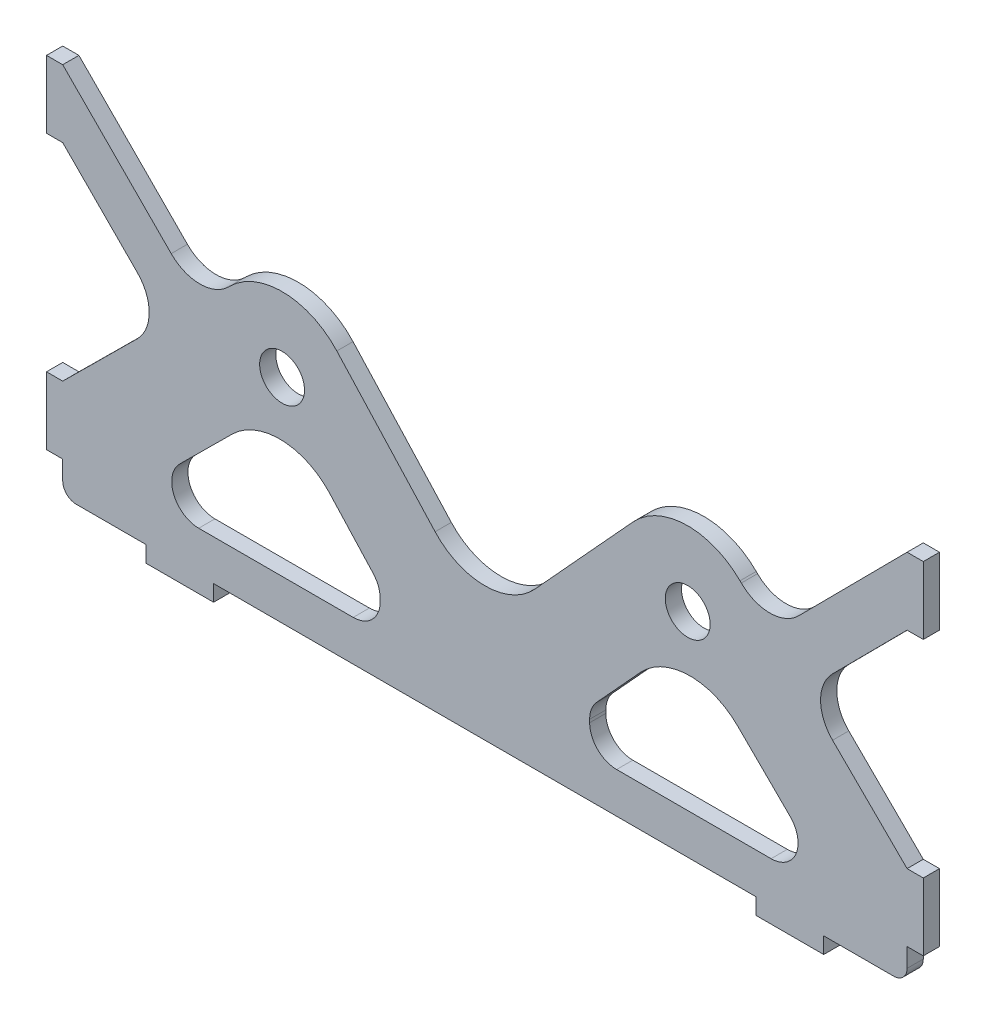
SolidWorks part; units mm, degrees
material "AISI 1020"
ref_plane "Front Plane" through (0, 0, 0) normal (0, 0, 1) x (1, 0, 0)
ref_plane "Top Plane" through (0, 0, 0) normal (0, 1, 0) x (1, 0, 0)
ref_plane "Right Plane" through (0, 0, 0) normal (1, 0, 0) x (0, 0, -1)
sketch "Sketch1" plane through (0, 0, 0) normal (0, 0, 1) x (1, 0, 0)
  line L1 (-79.4411, 19.05) -> (-79.4411, 57.404) construction
  line L5 (51.054, 0) -> (-51.054, 0)
  line L6 (-51.054, 0) -> (-51.054, -3.048)
  line L7 (-51.054, -3.048) -> (-63.754, -3.048)
  line L8 (-63.754, -3.048) -> (-63.754, 0)
  line L9 (-63.754, 0) -> (-76.9011, 0)
  line L10 (-79.4411, 2.54) -> (-79.4411, 6.096)
  line L11 (-79.4411, 6.096) -> (-82.4891, 6.096)
  line L12 (-82.4891, 6.096) -> (-82.4891, 18.796)
  line L13 (-82.4891, 18.796) -> (-79.4411, 18.796)
  line L15 (-82.4891, 19.05) -> (-82.4891, 57.404) construction
  line L16 (-64.008, -3.048) -> (-76.7741, -3.048) construction
  line L17 (-79.4411, 18.796) -> (-48.0051, 49.9833)
  line L18 (-27.8597, 49.4966) -> (0, 19.05)
  line L19 (-82.4891, 19.05) -> (-79.4411, 19.05) construction
  line L20 (-50.8, -3.048) -> (-50.8, 0) construction
  line L21 (-79.4411, 2.667) -> (-79.4411, 5.842) construction
  line L22 (0, -1000) -> (0, 49000) construction
  line L23 (27.8597, 49.4966) -> (0, 19.05)
  line L24 (79.4411, 18.796) -> (48.0051, 49.9833)
  line L25 (82.4891, 18.796) -> (79.4411, 18.796)
  line L26 (82.4891, 6.096) -> (82.4891, 18.796)
  line L27 (79.4411, 6.096) -> (82.4891, 6.096)
  line L28 (79.4411, 2.54) -> (79.4411, 6.096)
  line L29 (63.754, 0) -> (76.9011, 0)
  line L30 (63.754, -3.048) -> (63.754, 0)
  line L31 (51.054, -3.048) -> (63.754, -3.048)
  line L32 (51.054, 0) -> (51.054, -3.048)
  arc A0 (-27.8597, 49.4966) -> (-48.0051, 49.9833) centre (-38.1661, 40.0659) ccw
  arc A1 (-76.9011, 0) -> (-79.4411, 2.54) centre (-76.9011, 2.54) cw
  circle A2 centre (38.1661, 40.0659) radius 4.2227
  circle A3 centre (-38.1661, 40.0659) radius 4.2227
  circle A4 centre (-38.1661, 40.0659) radius 4.2227
  arc A5 (76.9011, 0) -> (79.4411, 2.54) centre (76.9011, 2.54) ccw
  arc A6 (27.8597, 49.4966) -> (48.0051, 49.9833) centre (38.1661, 40.0659) cw
  point P52 (0, 0)
  dimension "D2" = 27.94
  dimension "D7" = 2.54
  dimension "D1" = 12.7
  dimension "D4" = 19.05
  dimension "D5" = 0.254
  dimension "D6" = 0.254
  dimension "D3" = 0.254
extrude "Boss-Extrude1" add sketch "Sketch1" against normal blind 3.048 contours A2 | A4 | L17 A0 L18 L23 A6 L24 L25 L26 L27 L28 A5 L29 L30 L31 L32 L5 L6 L7 L8 L9 A1 L10 L11 L12 L13 region at (38.1661, 40.0659, 0) region at (-38.1661, 40.0659, 0)
fillet "Fillet1" radius 12.7 1 edges at (0, 19.05, -1.524)
sketch "Sketch3" plane through (0, 0, 0) normal (0, 0, 1) x (1, 0, 0)
  line L0 (-47.5534, 26.1015) -> (-66.1823, 7.62)
  line L2 (-66.1823, 7.62) -> (-19.7057, 7.62)
  line L3 (-19.7057, 7.62) -> (-19.7057, 15.24)
  line L4 (-19.7057, 15.24) -> (-29.2394, 25.6591)
  line L5 (-79.4411, 18.796) -> (-48.0051, 49.9833) construction
  line L6 (-27.8597, 49.4966) -> (-9.3695, 29.2895) construction
  line L8 (51.054, 0) -> (-51.054, 0) construction
  arc A0 (-47.5534, 26.1015) -> (-29.2394, 25.6591) centre (-38.6089, 17.0857) cw
  point P9 (0, 0)
  point P17 (-38.1661, 35.4146)
  dimension "D4" = 12.7
  dimension "D1" = 17.272
  dimension "D3" = 7.62
  dimension "D5" = 7.62
extrude "Cut-Extrude1" cut sketch "Sketch3" against normal through all both and the other way through all
fillet "Fillet2" radius 5.08 3 edges at (-19.7057, 7.62, -1.524) (-19.7057, 15.24, -1.524) (-66.1823, 7.62, -1.524)
mirror "Mirror1" about plane through (0, 0, 0) normal (1, 0, 0) of "Fillet2", "Cut-Extrude1"
sketch "Sketch4" plane through (0, 0, -3.048) normal (0, 0, -1) x (-1, 0, 0)
  line L0 (-82.4891, 70.358) -> (-79.4411, 70.358)
  line L1 (-79.4411, 70.358) -> (-53.6609, 44.3722)
  line L2 (-79.4411, 18.796) -> (-48.0051, 49.9833) construction
  line L3 (-53.6609, 44.3722) -> (-60.0107, 38.0727)
  line L4 (-60.0107, 38.0727) -> (-79.4411, 57.658)
  line L5 (-79.4411, 57.658) -> (-82.4891, 57.658)
  line L6 (-82.4891, 70.612) -> (-82.4891, 57.404) construction
  line L7 (-82.4891, 57.658) -> (-82.4891, 70.358)
  line L9 (-79.4411, 57.404) -> (-82.4891, 57.404) construction
  line L10 (-82.4891, 70.612) -> (-79.4411, 70.612) construction
  line L12 (-79.4411, 75.692) -> (-79.4411, 70.612) construction
  point P2 (0, 0)
  point P15 (0, 0)
  point P16 (-79.5606, 70.358)
  point P18 (0, 0)
  point P20 (0, 0)
  point P21 (-51.6982, 46.3194)
  dimension "D1" = 0.254
  dimension "D2" = 0.254
extrude "Boss-Extrude2" add sketch "Sketch4" against normal up to surface (3.048 mm away) up to face at (-34.343, 15.9682, 0)
mirror "Mirror3" about plane through (0, 0, 0) normal (1, 0, 0) of "Boss-Extrude2"
fillet "Fillet3" radius 7.62 4 edges at (60.0107, 38.0727, -1.524) (53.6609, 44.3722, -1.524) (-60.0107, 38.0727, -1.524) (-53.6609, 44.3722, -1.524)
